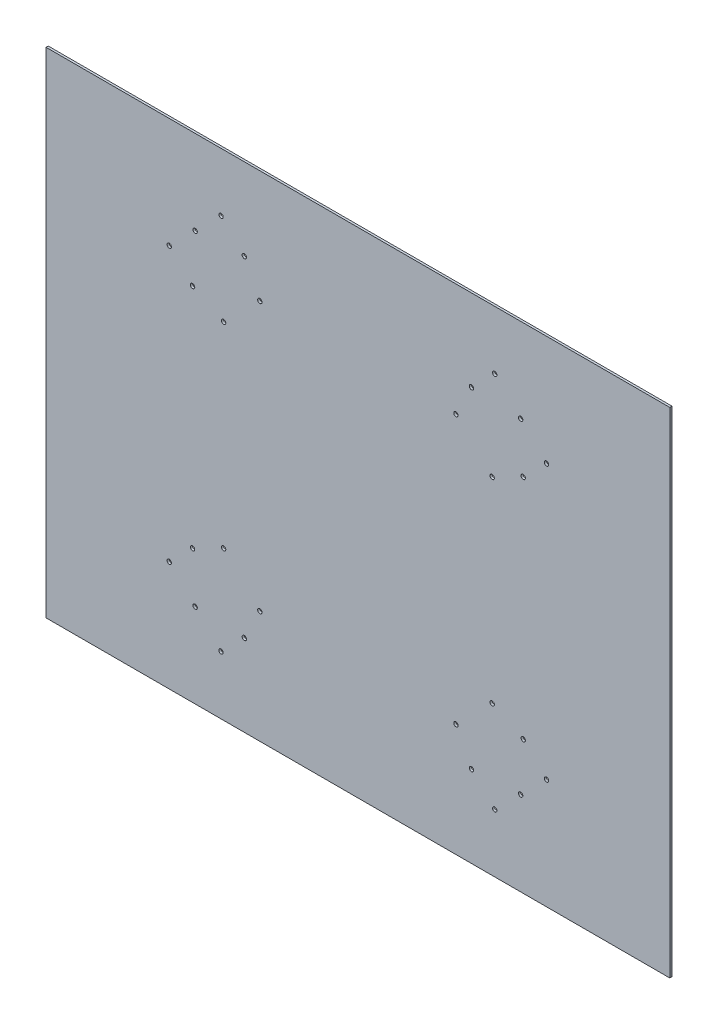
SolidWorks part; units mm, degrees
ref_plane "Front Plane" through (0, 0, 0) normal (0, 0, 1) x (1, 0, 0)
ref_plane "Top Plane" through (0, 0, 0) normal (0, 1, 0) x (1, 0, 0)
ref_plane "Right Plane" through (0, 0, 0) normal (1, 0, 0) x (0, 0, -1)
sketch "Sketch1" plane through (0, 0, 0) normal (0, 0, 1) x (1, 0, 0)
  line L4 (639.7773, -1841.7272) -> (1491.7773, -1841.7272)
  line L5 (639.7773, -1166.7272) -> (639.7773, -1841.7272)
  line L6 (1491.7773, -1166.7272) -> (639.7773, -1166.7272)
  line L7 (639.7773, -1166.7272) -> (639.7773, -1841.7272)
  line L12 (639.7773, -1841.7272) -> (1491.7773, -1841.7272)
  line L14 (1491.7773, -1166.7272) -> (639.7773, -1166.7272)
  line L20 (1491.7773, -1841.7272) -> (1491.7773, -1166.7272)
  line L21 (1491.7773, -1841.7272) -> (1491.7773, -1166.7272)
  circle A1 centre (1288.0916, -1281.9129) radius 3
  circle A2 centre (1288.0916, -1281.9129) radius 3
  circle A3 centre (843.4629, -1726.5416) radius 3
  circle A4 centre (843.4629, -1726.5416) radius 3
  circle A5 centre (931.8512, -1687.6507) radius 3
  circle A6 centre (931.8512, -1687.6507) radius 3
  circle A7 centre (910.638, -1730.0771) radius 3
  circle A8 centre (910.638, -1730.0771) radius 3
  circle A9 centre (878.8182, -1761.8969) radius 3
  circle A10 centre (878.8182, -1761.8969) radius 3
  circle A11 centre (1323.447, -1317.2682) radius 3
  circle A12 centre (1323.447, -1317.2682) radius 3
  circle A13 centre (1249.2008, -1370.3012) radius 3
  circle A14 centre (1249.2008, -1370.3012) radius 3
  circle A15 centre (1291.6272, -1349.088) radius 3
  circle A16 centre (1291.6272, -1349.088) radius 3
  circle A17 centre (1220.9165, -1278.3773) radius 3
  circle A18 centre (1220.9165, -1278.3773) radius 3
  circle A19 centre (1199.7033, -1320.8037) radius 3
  circle A20 centre (1199.7033, -1320.8037) radius 3
  circle A21 centre (1252.7363, -1246.5575) radius 3
  circle A22 centre (1252.7363, -1246.5575) radius 3
  circle A23 centre (882.3538, -1638.1533) radius 3
  circle A24 centre (882.3538, -1638.1533) radius 3
  circle A25 centre (808.1076, -1691.1863) radius 3
  circle A26 centre (808.1076, -1691.1863) radius 3
  circle A27 centre (839.9274, -1659.3665) radius 3
  circle A28 centre (839.9274, -1659.3665) radius 3
  circle A29 centre (1291.6272, -1659.3665) radius 3
  circle A30 centre (1291.6272, -1659.3665) radius 3
  circle A31 centre (1323.447, -1691.1863) radius 3
  circle A32 centre (1323.447, -1691.1863) radius 3
  circle A33 centre (1288.0916, -1726.5416) radius 3
  circle A34 centre (1288.0916, -1726.5416) radius 3
  circle A35 centre (1252.7363, -1761.8969) radius 3
  circle A36 centre (1252.7363, -1761.8969) radius 3
  circle A37 centre (1220.9165, -1730.0771) radius 3
  circle A38 centre (1220.9165, -1730.0771) radius 3
  circle A39 centre (1199.7033, -1687.6507) radius 3
  circle A40 centre (1199.7033, -1687.6507) radius 3
  circle A41 centre (1249.2008, -1638.1533) radius 3
  circle A42 centre (1249.2008, -1638.1533) radius 3
  circle A43 centre (839.9274, -1349.088) radius 3
  circle A44 centre (839.9274, -1349.088) radius 3
  circle A45 centre (808.1076, -1317.2682) radius 3
  circle A46 centre (808.1076, -1317.2682) radius 3
  circle A47 centre (843.4629, -1281.9129) radius 3
  circle A48 centre (843.4629, -1281.9129) radius 3
  circle A49 centre (878.8182, -1246.5575) radius 3
  circle A50 centre (878.8182, -1246.5575) radius 3
  circle A51 centre (910.638, -1278.3773) radius 3
  circle A52 centre (910.638, -1278.3773) radius 3
  circle A53 centre (931.8512, -1320.8037) radius 3
  circle A54 centre (931.8512, -1320.8037) radius 3
  circle A55 centre (882.3538, -1370.3012) radius 3
  circle A56 centre (882.3538, -1370.3012) radius 3
  dimension "D1" = 0
  dimension "D2" = 0
  dimension "D3" = 0
  dimension "D4" = 0
  dimension "D5" = 0
  dimension "D6" = 0
  dimension "D7" = 0
  dimension "D8" = 0
  dimension "D9" = 0
  dimension "D10" = 0
  dimension "D11" = 0
  dimension "D12" = 0
  dimension "D13" = 0
  dimension "D14" = 0
  dimension "D15" = 0
  dimension "D16" = 0
  dimension "D17" = 0
  dimension "D18" = 0
  dimension "D19" = 0
  dimension "D20" = 0
  dimension "D21" = 0
  dimension "D22" = 0
  dimension "D23" = 0
  dimension "D24" = 0
  dimension "D25" = 0
  dimension "D26" = 0
  dimension "D27" = 0
  dimension "D28" = 0
  dimension "D29" = 0
extrude "Boss-Extrude2" add sketch "Sketch1" along normal blind 3
